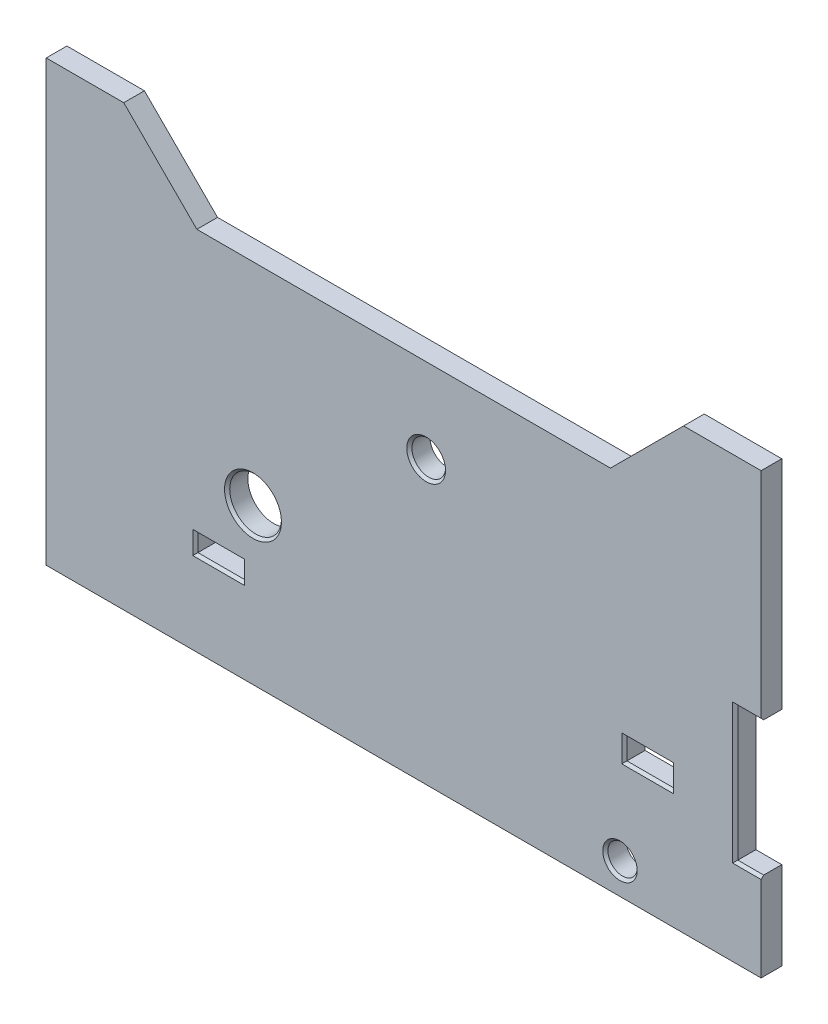
SolidWorks part; units mm, degrees
ref_plane "Front Plane" through (0, 0, 0) normal (0, 0, 1) x (1, 0, 0)
ref_plane "Top Plane" through (0, 0, 0) normal (0, 1, 0) x (1, 0, 0)
ref_plane "Right Plane" through (0, 0, 0) normal (1, 0, 0) x (0, 0, -1)
sketch "Sketch1" plane through (0, 0, 0) normal (0, 0, 1) x (1, 0, 0)
  line L2 (-86, -30) -> (-86, 30)
  line L6 (52.3, 13) -> (47.3, 13)
  line L7 (47.3, 13) -> (47.3, -13)
  line L8 (47.3, -13) -> (52.3, -13)
  line L11 (52.3, 30) -> (52.3, 13)
  line L12 (52.3, -13) -> (52.3, -30)
  line L23 (52.3, 30) -> (-86, 30)
  line L24 (25.85, -2.9) -> (34.85, -2.9)
  line L25 (25.85, -2.9) -> (25.85, -7.1)
  line L26 (25.85, -7.1) -> (34.85, -7.1)
  line L27 (34.85, -2.9) -> (34.85, -7.1)
  line L28 (25.85, -5) -> (34.85, -5) construction
  line L29 (30.35, -2.9) -> (30.35, -7.1) construction
  line L30 (-86, -30) -> (52.3, -30)
  line L31 (-48.15, -12) -> (-57.15, -12) construction
  line L32 (-57.15, -10.3) -> (-48.15, -10.3)
  line L33 (-57.15, -10.3) -> (-57.15, -13.7)
  line L34 (-57.15, -13.7) -> (-48.15, -13.7)
  line L35 (-48.15, -10.3) -> (-48.15, -13.7)
  line L36 (-52.65, -10.3) -> (-52.65, -14.5) construction
  circle A3 centre (-46, 0) radius 5
  circle A4 centre (25, -24) radius 2.83
  circle A5 centre (-12.5, 24.5) radius 3.25
  point P1 (-12, 0)
  point P31 (0, 0)
  point P33 (-52.65, -10.3)
  point P34 (0, 0)
  point P35 (-48.15, -12)
  point P36 (-57.15, -12)
  dimension "D5" = 10
  dimension "D17" = 5.66
  dimension "D25" = 6.5
  dimension "D1" = 40
  dimension "D8" = 26
  dimension "D13" = 9
  dimension "D14" = 4.2
  dimension "D18" = 111
  dimension "D27" = 33.5
  dimension "D28" = 24.5
  dimension "D6" = 5
  dimension "D4" = 24
  dimension "D7" = 116.35
  dimension "D9" = 60
  dimension "D3" = 138.3
  dimension "D10" = 5
  dimension "D11" = 12
  dimension "D12" = 33.35
extrude "Boss-Extrude1" add sketch "Sketch1" along normal mid plane 4
sketch "Sketch2" plane through (0, 0, 0) normal (0, 0, 1) x (1, 0, 0)
  line L0 (-86, 30) -> (52.3, 30)
  line L1 (52.3, 30) -> (52.3, 55)
  line L2 (52.3, 55) -> (37.3, 55)
  line L3 (37.3, 55) -> (23.1579, 40.8579)
  line L4 (23.1579, 40.8579) -> (-56.8579, 40.8579)
  line L5 (-56.8579, 40.8579) -> (-71, 55)
  line L6 (-71, 55) -> (-86, 55)
  line L7 (-86, 55) -> (-86, 30)
  dimension "D1" = 25
  dimension "D2" = 15
  dimension "D3" = 20
  dimension "D4" = 135
extrude "Boss-Extrude2" add sketch "Sketch2" along normal mid plane 4
sketch "Sketch3" plane through (0, 0, 2) normal (0, 0, 1) x (1, 0, 0)
  line L0 (25.85, -5) -> (34.85, -5) construction
  line L1 (25.85, -2.9) -> (25.85, -7.1) construction
  line L2 (34.85, -7.1) -> (34.85, -2.9) construction
  line L3 (30.35, -2.9) -> (30.35, -7.1) construction
  line L4 (34.85, -2.9) -> (25.85, -2.9) construction
  line L5 (25.85, -7.1) -> (34.85, -7.1) construction
  line L6 (-57.15, -12) -> (-48.15, -12) construction
  line L7 (-57.15, -10.3) -> (-57.15, -13.7) construction
  line L8 (-48.15, -13.7) -> (-48.15, -10.3) construction
  line L9 (-52.65, -10.3) -> (-52.65, -13.7) construction
  line L10 (-48.15, -10.3) -> (-57.15, -10.3) construction
  line L11 (-57.15, -13.7) -> (-48.15, -13.7) construction
sketch "Sketch4" plane through (47.3, 0, 0) normal (1, 0, 0) x (0, 0, -1)
  line L0 (-2, 0) -> (2, 0) construction
  line L1 (-2, -13) -> (-2, 13) construction
  line L2 (2, -13) -> (2, 13) construction
chamfer "Chamfer1" distance 0.5 angle 45 14 edges at (49.8, -13, 2) (49.8, 13, 2) (47.3, 0, 2) (27.83, -24, 2) (30.35, -7.1, 2) (25.85, -5, 2) (30.35, -2.9, 2) (34.85, -5, 2) (-48.15, -12, 2) (-52.65, -13.7, 2) (-57.15, -12, 2) (-52.65, -10.3, 2) (-41, 0, 2) (-9.25, 24.5, 2)
equation "\"back_boost\"= 7"
equation "\"D18@Sketch1\"=\"back_boost\"+104.00mm"
equation "\"D1@Sketch1\"=33.00mm+\"back_boost\""
equation "\"D7@Sketch1\"=109.35mm+\"back_boost\""
equation "\"D3@Sketch1\"=131.30mm+\"back_boost\""
equation "\"D12@Sketch1\"=\"back_boost\"+26.35mm"
equation "\"pin_hole_height\"=9"
equation "\"D13@Sketch1\"=\"pin_hole_height\""
equation "\"pin_hole_width\"=4.2"
equation "\"D14@Sketch1\"=\"pin_hole_width\""
